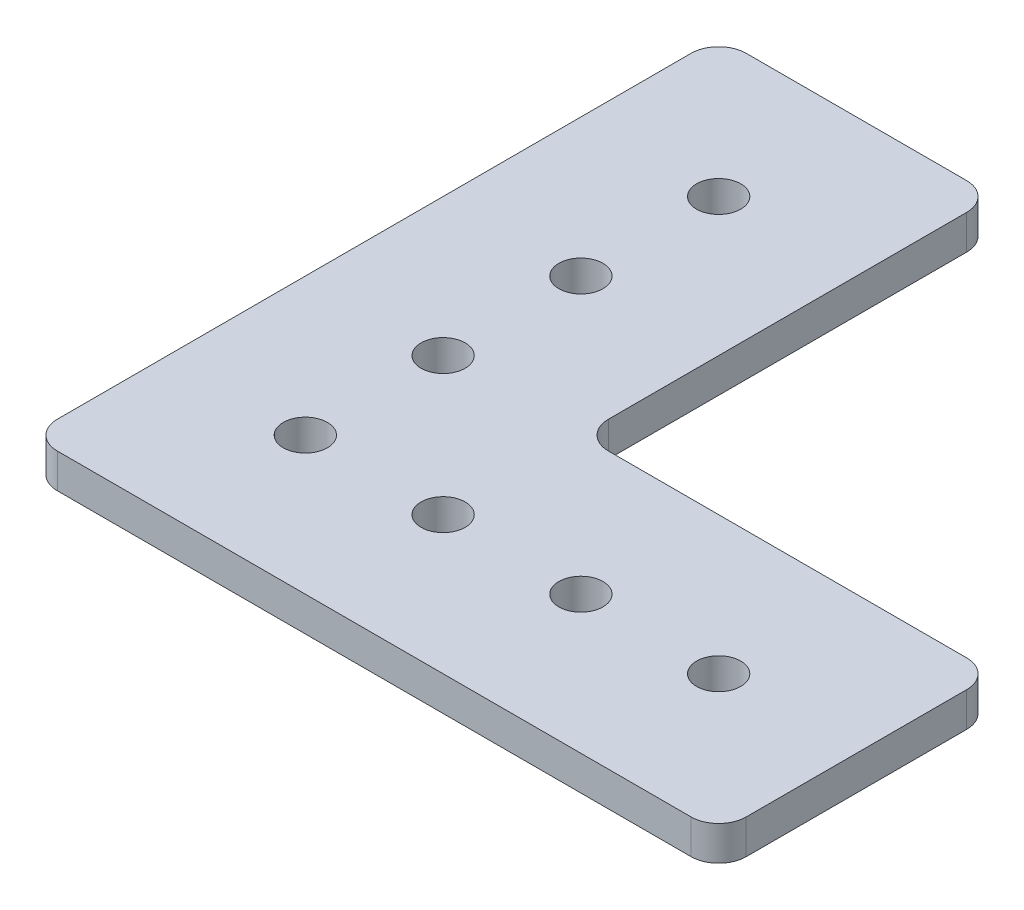
SolidWorks part; units mm, degrees
material "1060 Alloy"
ref_plane "Front Plane" through (0, 0, 0) normal (0, 0, 1) x (1, 0, 0)
ref_plane "Top Plane" through (0, 0, 0) normal (0, 1, 0) x (1, 0, 0)
ref_plane "Right Plane" through (0, 0, 0) normal (1, 0, 0) x (0, 0, -1)
sketch "Sketch1" plane through (0, 0, 0) normal (0, 1, 0) x (1, 0, 0)
  line L1 (2.54, 0) -> (25.4, 0)
  line L2 (0, 2.54) -> (0, 60.96)
  line L3 (2.54, 63.5) -> (22.86, 63.5)
  line L4 (25.4, 27.94) -> (25.4, 60.96)
  line L5 (0, 0) -> (60.96, 0)
  line L6 (0, 0) -> (0, 25.4)
  line L7 (27.94, 25.4) -> (60.96, 25.4)
  line L8 (63.5, 2.54) -> (63.5, 22.86)
  circle A0 centre (12.7, 12.7) radius 2.032
  circle A1 centre (25.4, 12.7) radius 2.032
  circle A2 centre (38.1, 12.7) radius 2.032
  circle A3 centre (50.8, 12.7) radius 2.032
  circle A4 centre (12.7, 25.4) radius 2.032
  circle A5 centre (12.7, 38.1) radius 2.032
  circle A6 centre (12.7, 50.8) radius 2.032
  arc A7 (0, 2.54) -> (2.54, 0) centre (2.54, 2.54) ccw
  arc A8 (60.96, 0) -> (63.5, 2.54) centre (60.96, 2.54) ccw
  arc A9 (63.5, 22.86) -> (60.96, 25.4) centre (60.96, 22.86) ccw
  arc A10 (27.94, 25.4) -> (25.4, 27.94) centre (27.94, 27.94) cw
  arc A11 (25.4, 60.96) -> (22.86, 63.5) centre (22.86, 60.96) ccw
  arc A12 (0, 60.96) -> (2.54, 63.5) centre (2.54, 60.96) cw
  point P28 (63.5, 0)
  point P31 (63.5, 25.4)
  point P36 (25.4, 63.5)
  point P39 (0, 63.5)
  dimension "D5" = 4.064
  dimension "D6" = 4.064
  dimension "D7" = 4.064
  dimension "D8" = 4.064
  dimension "D9" = 12.7
  dimension "D10" = 12.7
  dimension "D11" = 12.7
  dimension "D12" = 12.7
  dimension "D13" = 12.7
  dimension "D14" = 12.7
  dimension "D15" = 12.7
  dimension "D16" = 12.7
  dimension "D17" = 4.064
  dimension "D18" = 12.7
  dimension "D19" = 4.064
  dimension "D20" = 12.7
  dimension "D21" = 4.064
  dimension "D22" = 12.7
  dimension "D23" = 12.7
  dimension "D24" = 12.7
  dimension "D25" = 12.7
  dimension "D26" = 2.54
  dimension "D1" = 63.5
  dimension "D2" = 63.5
  dimension "D3" = 25.4
  dimension "D4" = 25.4
extrude "Boss-Extrude1" add sketch "Sketch1" along normal blind 3.175 contours A12 L2 A7 L1 L5 A8 L8 A9 L7 A10 L4 A11 L3 A6 A5 A4 A3 A2 A1 A0 region at (24.6283, 0, -24.6283)
